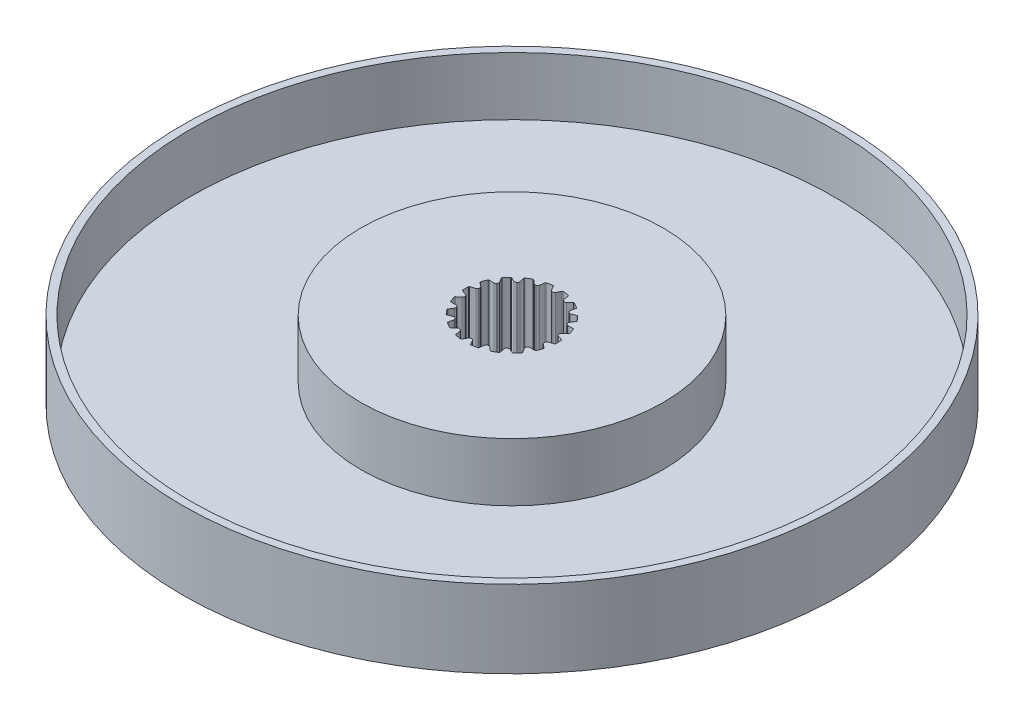
SolidWorks part; units mm, degrees
ref_plane "Front Plane" through (0, 0, 0) normal (0, 0, 1) x (1, 0, 0)
ref_plane "Top Plane" through (0, 0, 0) normal (0, 1, 0) x (1, 0, 0)
ref_plane "Right Plane" through (0, 0, 0) normal (1, 0, 0) x (0, 0, -1)
sketch "Sketch1" plane through (0, 0, 0) normal (0, 1, 0) x (1, 0, 0)
  circle A0 centre (0, 0) radius 42.5
  dimension "D1" = 85
extrude "Boss-Extrude1" add sketch "Sketch1" along normal blind 10
sketch "Sketch2" plane through (0, 10, 10) normal (0, 1, 0) x (1, 0, 0)
  line L1 (-5.2151, 8.5153) -> (-4.9419, 8.7287)
  line L3 (-5.0787, 9.5044) -> (-5.4084, 9.6115)
  line L5 (-5.4084, 10.3885) -> (-5.0787, 10.4956)
  line L7 (-4.9419, 11.2713) -> (-5.2151, 11.4847)
  line L9 (-4.9493, 12.2148) -> (-4.6029, 12.2027)
  line L11 (-4.2091, 12.8848) -> (-4.3928, 13.1788)
  line L13 (-3.8933, 13.774) -> (-3.5719, 13.6442)
  line L15 (-2.9686, 14.1504) -> (-3.0406, 14.4895)
  line L17 (-2.3677, 14.878) -> (-2.1101, 14.6461)
  line L19 (-1.37, 14.9154) -> (-1.3217, 15.2587)
  line L21 (-0.5566, 15.3937) -> (-0.3938, 15.0876)
  line L23 (0.3938, 15.0876) -> (0.5566, 15.3937)
  line L25 (1.3217, 15.2587) -> (1.37, 14.9154)
  line L27 (2.1101, 14.6461) -> (2.3677, 14.878)
  line L29 (3.0406, 14.4895) -> (2.9686, 14.1504)
  line L31 (3.5719, 13.6442) -> (3.8933, 13.774)
  line L33 (4.3928, 13.1788) -> (4.2091, 12.8848)
  line L35 (4.6029, 12.2027) -> (4.9493, 12.2148)
  line L37 (5.2151, 11.4847) -> (4.9419, 11.2713)
  line L39 (5.0787, 10.4956) -> (5.4084, 10.3885)
  line L41 (5.4084, 9.6115) -> (5.0787, 9.5044)
  line L43 (4.9419, 8.7287) -> (5.2151, 8.5153)
  line L45 (4.9493, 7.7852) -> (4.6029, 7.7973)
  line L47 (4.2091, 7.1152) -> (4.3928, 6.8212)
  line L49 (3.8933, 6.226) -> (3.5719, 6.3558)
  line L51 (2.9686, 5.8496) -> (3.0406, 5.5105)
  line L53 (2.3677, 5.122) -> (2.1101, 5.3539)
  line L55 (1.37, 5.0846) -> (1.3217, 4.7413)
  line L57 (0.5566, 4.6063) -> (0.3938, 4.9124)
  line L59 (-0.3938, 4.9124) -> (-0.5566, 4.6063)
  line L61 (-1.3217, 4.7413) -> (-1.37, 5.0846)
  line L63 (-2.1101, 5.3539) -> (-2.3677, 5.122)
  line L65 (-3.0406, 5.5105) -> (-2.9686, 5.8496)
  line L67 (-3.5719, 6.3558) -> (-3.8933, 6.226)
  line L69 (-4.3928, 6.8212) -> (-4.2091, 7.1152)
  line L71 (-4.6029, 7.7973) -> (-4.9493, 7.7852)
  circle A0 centre (0, 10) radius 42.5 construction
  arc A1 (-5.292, 8.2623) -> (-5.1709, 7.9295) centre (0, 10) ccw
  arc A3 (-5.2151, 8.5153) -> (-5.292, 8.2623) centre (-5.0735, 8.334) ccw
  arc A5 (-4.9419, 8.7287) -> (-4.8325, 9.0245) centre (-5.1266, 8.9651) ccw
  arc A7 (-4.8747, 9.2639) -> (-4.8325, 9.0245) centre (0, 10) ccw
  arc A9 (-4.8747, 9.2639) -> (-5.0787, 9.5044) centre (-5.1714, 9.2191) ccw
  arc A11 (-5.5672, 9.8229) -> (-5.4084, 9.6115) centre (-5.3373, 9.8302) ccw
  arc A13 (-5.5672, 10.1771) -> (-5.5672, 9.8229) centre (0, 10) ccw
  arc A15 (-5.4084, 10.3885) -> (-5.5672, 10.1771) centre (-5.3373, 10.1698) ccw
  arc A17 (-5.0787, 10.4956) -> (-4.8747, 10.7361) centre (-5.1714, 10.7809) ccw
  arc A19 (-4.8325, 10.9755) -> (-4.8747, 10.7361) centre (0, 10) ccw
  arc A21 (-4.8325, 10.9755) -> (-4.9419, 11.2713) centre (-5.1266, 11.0349) ccw
  arc A23 (-5.292, 11.7377) -> (-5.2151, 11.4847) centre (-5.0735, 11.666) ccw
  arc A25 (-5.1709, 12.0705) -> (-5.292, 11.7377) centre (0, 10) ccw
  arc A27 (-4.9493, 12.2148) -> (-5.1709, 12.0705) centre (-4.9574, 11.985) ccw
  arc A29 (-4.6029, 12.2027) -> (-4.329, 12.359) centre (-4.5924, 12.5026) ccw
  arc A31 (-4.2074, 12.5695) -> (-4.329, 12.359) centre (0, 10) ccw
  arc A33 (-4.2074, 12.5695) -> (-4.2091, 12.8848) centre (-4.4635, 12.7259) ccw
  arc A35 (-4.3785, 13.4429) -> (-4.3928, 13.1788) centre (-4.1977, 13.3007) ccw
  arc A37 (-4.1509, 13.7142) -> (-4.3785, 13.4429) centre (0, 10) ccw
  arc A39 (-3.8933, 13.774) -> (-4.1509, 13.7142) centre (-3.9795, 13.5608) ccw
  arc A41 (-3.5719, 13.6442) -> (-3.2611, 13.6973) centre (-3.4595, 13.9223) ccw
  arc A43 (-3.0749, 13.8536) -> (-3.2611, 13.6973) centre (0, 10) ccw
  arc A45 (-3.0749, 13.8536) -> (-2.9686, 14.1504) centre (-3.262, 14.0881) ccw
  arc A47 (-2.9369, 14.7328) -> (-3.0406, 14.4895) centre (-2.8157, 14.5374) ccw
  arc A49 (-2.6303, 14.9099) -> (-2.9369, 14.7328) centre (0, 10) ccw
  arc A51 (-2.3677, 14.878) -> (-2.6303, 14.9099) centre (-2.5216, 14.7071) ccw
  arc A53 (-2.1101, 14.6461) -> (-1.7998, 14.5897) centre (-1.9094, 14.869) ccw
  arc A55 (-1.5714, 14.6728) -> (-1.7998, 14.5897) centre (0, 10) ccw
  arc A57 (-1.5714, 14.6728) -> (-1.37, 14.9154) centre (-1.6671, 14.9572) ccw
  arc A59 (-1.1411, 15.4519) -> (-1.3217, 15.2587) centre (-1.094, 15.2267) ccw
  arc A61 (-0.7924, 15.5134) -> (-1.1411, 15.4519) centre (0, 10) ccw
  arc A63 (-0.5566, 15.3937) -> (-0.7924, 15.5134) centre (-0.7596, 15.2857) ccw
  arc A65 (-0.3938, 15.0876) -> (-0.1215, 14.9285) centre (-0.1289, 15.2284) ccw
  arc A67 (0.1215, 14.9285) -> (-0.1215, 14.9285) centre (0, 10) ccw
  arc A69 (0.1215, 14.9285) -> (0.3938, 15.0876) centre (0.1289, 15.2284) ccw
  arc A71 (0.7924, 15.5134) -> (0.5566, 15.3937) centre (0.7596, 15.2857) ccw
  arc A73 (1.1411, 15.4519) -> (0.7924, 15.5134) centre (0, 10) ccw
  arc A75 (1.3217, 15.2587) -> (1.1411, 15.4519) centre (1.094, 15.2267) ccw
  arc A77 (1.37, 14.9154) -> (1.5714, 14.6728) centre (1.6671, 14.9572) ccw
  arc A79 (1.7998, 14.5897) -> (1.5714, 14.6728) centre (0, 10) ccw
  arc A81 (1.7998, 14.5897) -> (2.1101, 14.6461) centre (1.9094, 14.869) ccw
  arc A83 (2.6303, 14.9099) -> (2.3677, 14.878) centre (2.5216, 14.7071) ccw
  arc A85 (2.9369, 14.7328) -> (2.6303, 14.9099) centre (0, 10) ccw
  arc A87 (3.0406, 14.4895) -> (2.9369, 14.7328) centre (2.8157, 14.5374) ccw
  arc A89 (2.9686, 14.1504) -> (3.0749, 13.8536) centre (3.262, 14.0881) ccw
  arc A91 (3.2611, 13.6973) -> (3.0749, 13.8536) centre (0, 10) ccw
  arc A93 (3.2611, 13.6973) -> (3.5719, 13.6442) centre (3.4595, 13.9223) ccw
  arc A95 (4.1509, 13.7142) -> (3.8933, 13.774) centre (3.9795, 13.5608) ccw
  arc A97 (4.3785, 13.4429) -> (4.1509, 13.7142) centre (0, 10) ccw
  arc A99 (4.3928, 13.1788) -> (4.3785, 13.4429) centre (4.1977, 13.3007) ccw
  arc A101 (4.2091, 12.8848) -> (4.2074, 12.5695) centre (4.4635, 12.7259) ccw
  arc A103 (4.329, 12.359) -> (4.2074, 12.5695) centre (0, 10) ccw
  arc A105 (4.329, 12.359) -> (4.6029, 12.2027) centre (4.5924, 12.5026) ccw
  arc A107 (5.1709, 12.0705) -> (4.9493, 12.2148) centre (4.9574, 11.985) ccw
  arc A109 (5.292, 11.7377) -> (5.1709, 12.0705) centre (0, 10) ccw
  arc A111 (5.2151, 11.4847) -> (5.292, 11.7377) centre (5.0735, 11.666) ccw
  arc A113 (4.9419, 11.2713) -> (4.8325, 10.9755) centre (5.1266, 11.0349) ccw
  arc A115 (4.8747, 10.7361) -> (4.8325, 10.9755) centre (0, 10) ccw
  arc A117 (4.8747, 10.7361) -> (5.0787, 10.4956) centre (5.1714, 10.7809) ccw
  arc A119 (5.5672, 10.1771) -> (5.4084, 10.3885) centre (5.3373, 10.1698) ccw
  arc A121 (5.5672, 9.8229) -> (5.5672, 10.1771) centre (0, 10) ccw
  arc A123 (5.4084, 9.6115) -> (5.5672, 9.8229) centre (5.3373, 9.8302) ccw
  arc A125 (5.0787, 9.5044) -> (4.8747, 9.2639) centre (5.1714, 9.2191) ccw
  arc A127 (4.8325, 9.0245) -> (4.8747, 9.2639) centre (0, 10) ccw
  arc A129 (4.8325, 9.0245) -> (4.9419, 8.7287) centre (5.1266, 8.9651) ccw
  arc A131 (5.292, 8.2623) -> (5.2151, 8.5153) centre (5.0735, 8.334) ccw
  arc A133 (5.1709, 7.9295) -> (5.292, 8.2623) centre (0, 10) ccw
  arc A135 (4.9493, 7.7852) -> (5.1709, 7.9295) centre (4.9574, 8.015) ccw
  arc A137 (4.6029, 7.7973) -> (4.329, 7.641) centre (4.5924, 7.4974) ccw
  arc A139 (4.2074, 7.4305) -> (4.329, 7.641) centre (0, 10) ccw
  arc A141 (4.2074, 7.4305) -> (4.2091, 7.1152) centre (4.4635, 7.2741) ccw
  arc A143 (4.3785, 6.5571) -> (4.3928, 6.8212) centre (4.1977, 6.6993) ccw
  arc A145 (4.1509, 6.2858) -> (4.3785, 6.5571) centre (0, 10) ccw
  arc A147 (3.8933, 6.226) -> (4.1509, 6.2858) centre (3.9795, 6.4392) ccw
  arc A149 (3.5719, 6.3558) -> (3.2611, 6.3027) centre (3.4595, 6.0777) ccw
  arc A151 (3.0749, 6.1464) -> (3.2611, 6.3027) centre (0, 10) ccw
  arc A153 (3.0749, 6.1464) -> (2.9686, 5.8496) centre (3.262, 5.9119) ccw
  arc A155 (2.9369, 5.2672) -> (3.0406, 5.5105) centre (2.8157, 5.4626) ccw
  arc A157 (2.6303, 5.0901) -> (2.9369, 5.2672) centre (0, 10) ccw
  arc A159 (2.3677, 5.122) -> (2.6303, 5.0901) centre (2.5216, 5.2929) ccw
  arc A161 (2.1101, 5.3539) -> (1.7998, 5.4103) centre (1.9094, 5.131) ccw
  arc A163 (1.5714, 5.3272) -> (1.7998, 5.4103) centre (0, 10) ccw
  arc A165 (1.5714, 5.3272) -> (1.37, 5.0846) centre (1.6671, 5.0428) ccw
  arc A167 (1.1411, 4.5481) -> (1.3217, 4.7413) centre (1.094, 4.7733) ccw
  arc A169 (0.7924, 4.4866) -> (1.1411, 4.5481) centre (0, 10) ccw
  arc A171 (0.5566, 4.6063) -> (0.7924, 4.4866) centre (0.7596, 4.7143) ccw
  arc A173 (0.3938, 4.9124) -> (0.1215, 5.0715) centre (0.1289, 4.7716) ccw
  arc A175 (-0.1215, 5.0715) -> (0.1215, 5.0715) centre (0, 10) ccw
  arc A177 (-0.1215, 5.0715) -> (-0.3938, 4.9124) centre (-0.1289, 4.7716) ccw
  arc A179 (-0.7924, 4.4866) -> (-0.5566, 4.6063) centre (-0.7596, 4.7143) ccw
  arc A181 (-1.1411, 4.5481) -> (-0.7924, 4.4866) centre (0, 10) ccw
  arc A183 (-1.3217, 4.7413) -> (-1.1411, 4.5481) centre (-1.094, 4.7733) ccw
  arc A185 (-1.37, 5.0846) -> (-1.5714, 5.3272) centre (-1.6671, 5.0428) ccw
  arc A187 (-1.7998, 5.4103) -> (-1.5714, 5.3272) centre (0, 10) ccw
  arc A189 (-1.7998, 5.4103) -> (-2.1101, 5.3539) centre (-1.9094, 5.131) ccw
  arc A191 (-2.6303, 5.0901) -> (-2.3677, 5.122) centre (-2.5216, 5.2929) ccw
  arc A193 (-2.9369, 5.2672) -> (-2.6303, 5.0901) centre (0, 10) ccw
  arc A195 (-3.0406, 5.5105) -> (-2.9369, 5.2672) centre (-2.8157, 5.4626) ccw
  arc A197 (-2.9686, 5.8496) -> (-3.0749, 6.1464) centre (-3.262, 5.9119) ccw
  arc A199 (-3.2611, 6.3027) -> (-3.0749, 6.1464) centre (0, 10) ccw
  arc A201 (-3.2611, 6.3027) -> (-3.5719, 6.3558) centre (-3.4595, 6.0777) ccw
  arc A203 (-4.1509, 6.2858) -> (-3.8933, 6.226) centre (-3.9795, 6.4392) ccw
  arc A205 (-4.3785, 6.5571) -> (-4.1509, 6.2858) centre (0, 10) ccw
  arc A207 (-4.3928, 6.8212) -> (-4.3785, 6.5571) centre (-4.1977, 6.6993) ccw
  arc A209 (-4.2091, 7.1152) -> (-4.2074, 7.4305) centre (-4.4635, 7.2741) ccw
  arc A211 (-4.329, 7.641) -> (-4.2074, 7.4305) centre (0, 10) ccw
  arc A213 (-4.329, 7.641) -> (-4.6029, 7.7973) centre (-4.5924, 7.4974) ccw
  arc A215 (-5.1709, 7.9295) -> (-4.9493, 7.7852) centre (-4.9574, 8.015) ccw
  dimension "D1" = 0
extrude "Cut-Extrude1" [suppressed] cut sketch "Sketch2" against normal blind 10
sketch "Sketch3" plane through (0, 10, 0) normal (0, 1, 0) x (1, 0, 0)
  circle A0 centre (0, 0) radius 19.5
  circle A1 centre (0, 0) radius 41.5
  dimension "D1" = 83
  dimension "D2" = 39
extrude "Cut-Extrude2" cut sketch "Sketch3" against normal blind 7.5
sketch "Sketch4" plane through (0, 10, 0) normal (0, 1, 0) x (1, 0, 0)
  line L0 (0, 0) -> (0, 6) construction
  line L1 (-0.5673, 5.9104) -> (-0.2707, 5.3527)
  line L2 (-0.05, 5.22) -> (0.05, 5.22)
  line L3 (0.2707, 5.3527) -> (0.5673, 5.9104)
  line L4 (0, 0) -> (-0.6667, 5.9628) construction
  line L5 (0, 0) -> (1.4129, 5.8313) construction
  line L6 (1.4884, 5.748) -> (1.5763, 5.1225)
  line L7 (1.7384, 4.9223) -> (1.8323, 4.8881)
  line L8 (2.0851, 4.9373) -> (2.5546, 5.3599)
  line L9 (3.3646, 4.8923) -> (3.2332, 4.2744)
  line L10 (3.3171, 4.0309) -> (3.3937, 3.9666)
  line L11 (3.648, 3.9263) -> (4.2337, 4.163)
  line L12 (4.8349, 3.4465) -> (4.5002, 2.9108)
  line L13 (4.4957, 2.6533) -> (4.5457, 2.5667)
  line L14 (4.7709, 2.4419) -> (5.4022, 2.4639)
  line L15 (5.7221, 1.585) -> (5.2243, 1.1961)
  line L16 (5.132, 0.9557) -> (5.1494, 0.8572)
  line L17 (5.3184, 0.6629) -> (5.9191, 0.4677)
  line L18 (5.9191, -0.4677) -> (5.3184, -0.6629)
  line L19 (5.1494, -0.8572) -> (5.132, -0.9557)
  line L20 (5.2243, -1.1961) -> (5.7221, -1.585)
  line L21 (5.4022, -2.4639) -> (4.7709, -2.4419)
  line L22 (4.5457, -2.5667) -> (4.4957, -2.6533)
  line L23 (4.5002, -2.9108) -> (4.8349, -3.4465)
  line L24 (4.2337, -4.163) -> (3.648, -3.9263)
  line L25 (3.3937, -3.9666) -> (3.3171, -4.0309)
  line L26 (3.2332, -4.2744) -> (3.3646, -4.8923)
  line L27 (2.5546, -5.3599) -> (2.0851, -4.9373)
  line L28 (1.8323, -4.8881) -> (1.7384, -4.9223)
  line L29 (1.5763, -5.1225) -> (1.4884, -5.748)
  line L30 (0.5673, -5.9104) -> (0.2707, -5.3527)
  line L31 (0.05, -5.22) -> (-0.05, -5.22)
  line L32 (-0.2707, -5.3527) -> (-0.5673, -5.9104)
  line L33 (-1.4884, -5.748) -> (-1.5763, -5.1225)
  line L34 (-1.7384, -4.9223) -> (-1.8323, -4.8881)
  line L35 (-2.0851, -4.9373) -> (-2.5546, -5.3599)
  line L36 (-3.3646, -4.8923) -> (-3.2332, -4.2744)
  line L37 (-3.3171, -4.0309) -> (-3.3937, -3.9666)
  line L38 (-3.648, -3.9263) -> (-4.2337, -4.163)
  line L39 (-4.8349, -3.4465) -> (-4.5002, -2.9108)
  line L40 (-4.4957, -2.6533) -> (-4.5457, -2.5667)
  line L41 (-4.7709, -2.4419) -> (-5.4022, -2.4639)
  line L42 (-5.7221, -1.585) -> (-5.2243, -1.1961)
  line L43 (-5.132, -0.9557) -> (-5.1494, -0.8572)
  line L44 (-5.3184, -0.6629) -> (-5.9191, -0.4677)
  line L45 (-5.9191, 0.4677) -> (-5.3184, 0.6629)
  line L46 (-5.1494, 0.8572) -> (-5.132, 0.9557)
  line L47 (-5.2243, 1.1961) -> (-5.7221, 1.585)
  line L48 (-5.4022, 2.4639) -> (-4.7709, 2.4419)
  line L49 (-4.5457, 2.5667) -> (-4.4957, 2.6533)
  line L50 (-4.5002, 2.9108) -> (-4.8349, 3.4465)
  line L51 (-4.2337, 4.163) -> (-3.648, 3.9263)
  line L52 (-3.3937, 3.9666) -> (-3.3171, 4.0309)
  line L53 (-3.2332, 4.2744) -> (-3.3646, 4.8923)
  line L54 (-2.5546, 5.3599) -> (-2.0851, 4.9373)
  line L55 (-1.8323, 4.8881) -> (-1.7384, 4.9223)
  line L56 (-1.5763, 5.1225) -> (-1.4884, 5.748)
  arc A1 (0.05, 5.22) -> (0.2707, 5.3527) centre (0.05, 5.47) ccw
  arc A2 (-0.2707, 5.3527) -> (-0.05, 5.22) centre (-0.05, 5.47) ccw
  arc A5 (-0.6667, 5.9628) -> (0.6667, 5.9628) centre (0, 0) ccw construction
  arc A6 (0.5673, 5.9104) -> (0.6667, 5.9628) centre (0.6556, 5.8635) cw
  arc A7 (-0.5673, 5.9104) -> (-0.6667, 5.9628) centre (-0.6556, 5.8635) ccw
  arc A8 (1.8323, 4.8881) -> (2.0851, 4.9373) centre (1.9178, 5.123) ccw
  arc A9 (1.5763, 5.1225) -> (1.7384, 4.9223) centre (1.8239, 5.1572) ccw
  arc A10 (2.5546, 5.3599) -> (2.6659, 5.3752) centre (2.6215, 5.2856) cw
  arc A11 (1.4884, 5.748) -> (1.4129, 5.8313) centre (1.3894, 5.7341) ccw
  arc A12 (3.3937, 3.9666) -> (3.648, 3.9263) centre (3.5544, 4.1581) ccw
  arc A13 (3.2332, 4.2744) -> (3.3171, 4.0309) centre (3.4778, 4.2224) ccw
  arc A14 (4.2337, 4.163) -> (4.3436, 4.1393) centre (4.2712, 4.0703) cw
  arc A15 (3.3646, 4.8923) -> (3.3221, 4.9964) centre (3.2667, 4.9131) ccw
  arc A16 (4.5457, 2.5667) -> (4.7709, 2.4419) centre (4.7622, 2.6917) ccw
  arc A17 (4.5002, 2.9108) -> (4.4957, 2.6533) centre (4.7122, 2.7783) ccw
  arc A18 (5.4022, 2.4639) -> (5.4973, 2.404) centre (5.4057, 2.364) cw
  arc A19 (4.8349, 3.4465) -> (4.8306, 3.5588) centre (4.7501, 3.4995) ccw
  arc A20 (5.1494, 0.8572) -> (5.3184, 0.6629) centre (5.3956, 0.9006) ccw
  arc A21 (5.2243, 1.1961) -> (5.132, 0.9557) centre (5.3782, 0.9991) ccw
  arc A22 (5.9191, 0.4677) -> (5.988, 0.3789) centre (5.8882, 0.3725) cw
  arc A23 (5.7221, 1.585) -> (5.7565, 1.692) centre (5.6605, 1.6638) ccw
  arc A24 (5.132, -0.9557) -> (5.2243, -1.1961) centre (5.3782, -0.9991) ccw
  arc A25 (5.3184, -0.6629) -> (5.1494, -0.8572) centre (5.3956, -0.9006) ccw
  arc A26 (5.7221, -1.585) -> (5.7565, -1.692) centre (5.6605, -1.6638) cw
  arc A27 (5.9191, -0.4677) -> (5.988, -0.3789) centre (5.8882, -0.3725) ccw
  arc A28 (4.4957, -2.6533) -> (4.5002, -2.9108) centre (4.7122, -2.7783) ccw
  arc A29 (4.7709, -2.4419) -> (4.5457, -2.5667) centre (4.7622, -2.6917) ccw
  arc A30 (4.8349, -3.4465) -> (4.8306, -3.5588) centre (4.7501, -3.4995) cw
  arc A31 (5.4022, -2.4639) -> (5.4973, -2.404) centre (5.4057, -2.364) ccw
  arc A32 (3.3171, -4.0309) -> (3.2332, -4.2744) centre (3.4778, -4.2224) ccw
  arc A33 (3.648, -3.9263) -> (3.3937, -3.9666) centre (3.5544, -4.1581) ccw
  arc A34 (3.3646, -4.8923) -> (3.3221, -4.9964) centre (3.2667, -4.9131) cw
  arc A35 (4.2337, -4.163) -> (4.3436, -4.1393) centre (4.2712, -4.0703) ccw
  arc A36 (1.7384, -4.9223) -> (1.5763, -5.1225) centre (1.8239, -5.1572) ccw
  arc A37 (2.0851, -4.9373) -> (1.8323, -4.8881) centre (1.9178, -5.123) ccw
  arc A38 (1.4884, -5.748) -> (1.4129, -5.8313) centre (1.3894, -5.7341) cw
  arc A39 (2.5546, -5.3599) -> (2.6659, -5.3752) centre (2.6215, -5.2856) ccw
  arc A40 (-0.05, -5.22) -> (-0.2707, -5.3527) centre (-0.05, -5.47) ccw
  arc A41 (0.2707, -5.3527) -> (0.05, -5.22) centre (0.05, -5.47) ccw
  arc A42 (-0.5673, -5.9104) -> (-0.6667, -5.9628) centre (-0.6556, -5.8635) cw
  arc A43 (0.5673, -5.9104) -> (0.6667, -5.9628) centre (0.6556, -5.8635) ccw
  arc A44 (-1.8323, -4.8881) -> (-2.0851, -4.9373) centre (-1.9178, -5.123) ccw
  arc A45 (-1.5763, -5.1225) -> (-1.7384, -4.9223) centre (-1.8239, -5.1572) ccw
  arc A46 (-2.5546, -5.3599) -> (-2.6659, -5.3752) centre (-2.6215, -5.2856) cw
  arc A47 (-1.4884, -5.748) -> (-1.4129, -5.8313) centre (-1.3894, -5.7341) ccw
  arc A48 (-3.3937, -3.9666) -> (-3.648, -3.9263) centre (-3.5544, -4.1581) ccw
  arc A49 (-3.2332, -4.2744) -> (-3.3171, -4.0309) centre (-3.4778, -4.2224) ccw
  arc A50 (-4.2337, -4.163) -> (-4.3436, -4.1393) centre (-4.2712, -4.0703) cw
  arc A51 (-3.3646, -4.8923) -> (-3.3221, -4.9964) centre (-3.2667, -4.9131) ccw
  arc A52 (-4.5457, -2.5667) -> (-4.7709, -2.4419) centre (-4.7622, -2.6917) ccw
  arc A53 (-4.5002, -2.9108) -> (-4.4957, -2.6533) centre (-4.7122, -2.7783) ccw
  arc A54 (-5.4022, -2.4639) -> (-5.4973, -2.404) centre (-5.4057, -2.364) cw
  arc A55 (-4.8349, -3.4465) -> (-4.8306, -3.5588) centre (-4.7501, -3.4995) ccw
  arc A56 (-5.1494, -0.8572) -> (-5.3184, -0.6629) centre (-5.3956, -0.9006) ccw
  arc A57 (-5.2243, -1.1961) -> (-5.132, -0.9557) centre (-5.3782, -0.9991) ccw
  arc A58 (-5.9191, -0.4677) -> (-5.988, -0.3789) centre (-5.8882, -0.3725) cw
  arc A59 (-5.7221, -1.585) -> (-5.7565, -1.692) centre (-5.6605, -1.6638) ccw
  arc A60 (-5.132, 0.9557) -> (-5.2243, 1.1961) centre (-5.3782, 0.9991) ccw
  arc A61 (-5.3184, 0.6629) -> (-5.1494, 0.8572) centre (-5.3956, 0.9006) ccw
  arc A62 (-5.7221, 1.585) -> (-5.7565, 1.692) centre (-5.6605, 1.6638) cw
  arc A63 (-5.9191, 0.4677) -> (-5.988, 0.3789) centre (-5.8882, 0.3725) ccw
  arc A64 (-4.4957, 2.6533) -> (-4.5002, 2.9108) centre (-4.7122, 2.7783) ccw
  arc A65 (-4.7709, 2.4419) -> (-4.5457, 2.5667) centre (-4.7622, 2.6917) ccw
  arc A66 (-4.8349, 3.4465) -> (-4.8306, 3.5588) centre (-4.7501, 3.4995) cw
  arc A67 (-5.4022, 2.4639) -> (-5.4973, 2.404) centre (-5.4057, 2.364) ccw
  arc A68 (-3.3171, 4.0309) -> (-3.2332, 4.2744) centre (-3.4778, 4.2224) ccw
  arc A69 (-3.648, 3.9263) -> (-3.3937, 3.9666) centre (-3.5544, 4.1581) ccw
  arc A70 (-3.3646, 4.8923) -> (-3.3221, 4.9964) centre (-3.2667, 4.9131) cw
  arc A71 (-4.2337, 4.163) -> (-4.3436, 4.1393) centre (-4.2712, 4.0703) ccw
  arc A72 (-1.7384, 4.9223) -> (-1.5763, 5.1225) centre (-1.8239, 5.1572) ccw
  arc A73 (-2.0851, 4.9373) -> (-1.8323, 4.8881) centre (-1.9178, 5.123) ccw
  arc A74 (-1.4884, 5.748) -> (-1.4129, 5.8313) centre (-1.3894, 5.7341) cw
  arc A75 (-2.5546, 5.3599) -> (-2.6659, 5.3752) centre (-2.6215, 5.2856) ccw
  arc A76 (0.6667, 5.9628) -> (1.4129, 5.8313) centre (0, 0) cw
  arc A77 (2.6659, 5.3752) -> (3.3221, 4.9964) centre (0, 0) cw
  arc A78 (4.3436, 4.1393) -> (4.8306, 3.5588) centre (0, 0) cw
  arc A79 (5.4973, 2.404) -> (5.7565, 1.692) centre (0, 0) cw
  arc A80 (5.988, 0.3789) -> (5.988, -0.3789) centre (0, 0) cw
  arc A81 (5.7565, -1.692) -> (5.4973, -2.404) centre (0, 0) cw
  arc A82 (4.8306, -3.5588) -> (4.3436, -4.1393) centre (0, 0) cw
  arc A83 (3.3221, -4.9964) -> (2.6659, -5.3752) centre (0, 0) cw
  arc A84 (1.4129, -5.8313) -> (0.6667, -5.9628) centre (0, 0) cw
  arc A85 (-0.6667, -5.9628) -> (-1.4129, -5.8313) centre (0, 0) cw
  arc A86 (-2.6659, -5.3752) -> (-3.3221, -4.9964) centre (0, 0) cw
  arc A87 (-4.3436, -4.1393) -> (-4.8306, -3.5588) centre (0, 0) cw
  arc A88 (-5.4973, -2.404) -> (-5.7565, -1.692) centre (0, 0) cw
  arc A89 (-5.988, -0.3789) -> (-5.988, 0.3789) centre (0, 0) cw
  arc A90 (-5.7565, 1.692) -> (-5.4973, 2.404) centre (0, 0) cw
  arc A91 (-4.8306, 3.5588) -> (-4.3436, 4.1393) centre (0, 0) cw
  arc A92 (-3.3221, 4.9964) -> (-2.6659, 5.3752) centre (0, 0) cw
  arc A93 (-1.4129, 5.8313) -> (-0.6667, 5.9628) centre (0, 0) cw
  point P14 (0.2002, 5.22)
  point P17 (-0.2002, 5.22)
  point P225 (0, 0)
  point P260 (0, 0)
  dimension "D6" = 0.25
  dimension "D7" = 12
  dimension "D10" = 0.1
  dimension "D2" = 28
  dimension "D3" = 28
  dimension "D4" = 0.05
  dimension "D5" = 5.22
  dimension "D8" = 0.1
  dimension "D9" = 20
  dimension "D11" = 18
  dimension "D12" = 18
extrude "Cut-Extrude4" cut sketch "Sketch4" against normal through all contours A93 A74 L56 A72 L55 A73 L54 A75 A92 A70 L53 A68 L52 A69 L51 A71 A91 A66 L50 A64 L49 A65 L48 A67 A90 A62 L47 A60 L46 A61 L45 A63 A89 A58 L44 A56 L43 A57 L42 A59 A88 A54 L41 A52 L40 A53 L39 A55 A87 A50 L38 region at (0, 10, 0)
